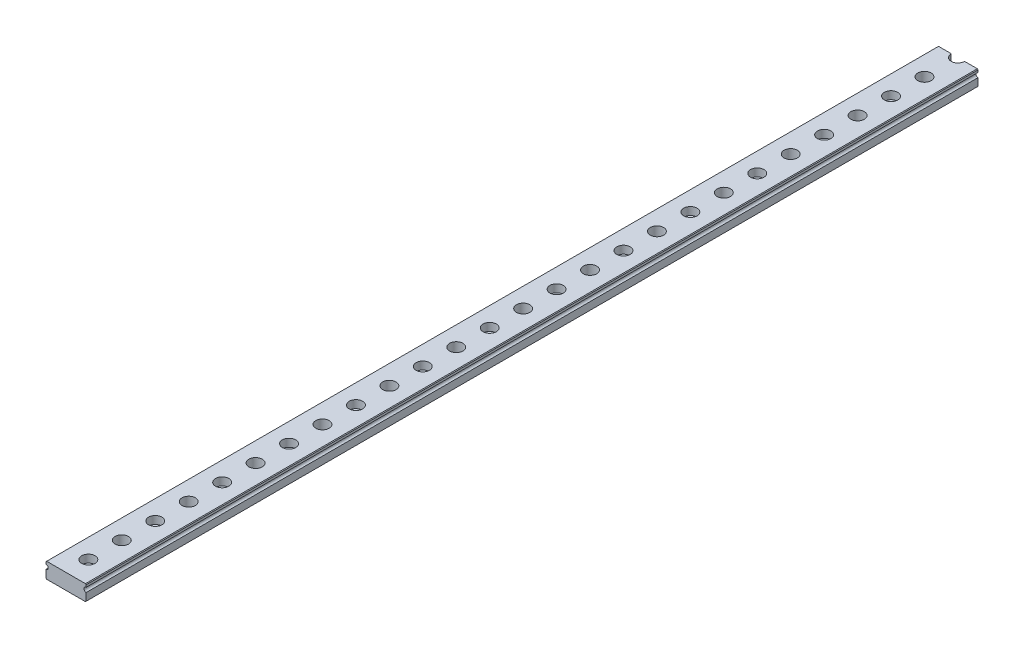
SolidWorks part; units mm, degrees
material "AISI 1020"
ref_plane "Front Plane" through (0, 0, 0) normal (0, 0, 1) x (1, 0, 0)
ref_plane "Top Plane" through (0, 0, 0) normal (0, 1, 0) x (1, 0, 0)
ref_plane "Right Plane" through (0, 0, 0) normal (1, 0, 0) x (0, 0, -1)
ref_plane "Plano1" through (0, 0, 0) normal (0, -1, 0) x (1, 0, 0)
sketch "Esboço1" plane through (0, 0, 0) normal (0, -1, 0) x (1, 0, 0)
  line L0 (-18, -400) -> (0, -400)
  line L1 (0, -400) -> (0, 0)
  line L2 (0, 0) -> (-18, 0)
  line L3 (-18, 0) -> (-18, -400)
  dimension "D1" = 400
  dimension "D2" = 18
extrude "Ressalto-extrusão1" add sketch "Esboço1" against normal blind 7
hole_wizard "Furo de diâmetro Ø2.0 (2)1" positions "Esboço5" profile "Esboço4" hole size "Ø2.0" standard "Ansi Metric" end condition through all
sketch "Esboço5" plane through (0, 0, -400) normal (0, 0, -1) x (-1, 0, 0)
  line L0 (0, 0) -> (18, 0) construction
  line L1 (18, 7) -> (18, 0) construction
  point P0 (0, 4.7)
  point P1 (18, 4.7)
  dimension "D1" = 18
  dimension "D2" = 4.7
sketch "Esboço4" plane through (0, 4.7, -400) normal (1, 0, 0) x (0, 1, 0)
  line L0 (0, 0) -> (0, 400)
  line L1 (0, 400) -> (1, 400)
  line L2 (1, 400) -> (1, 0)
  line L5 (1, 0) -> (0, 0)
  line L11 (0, -6.35) -> (0, 107.95) construction
  dimension "Thru Hole Dia." = 2
  dimension "Thru Hole Depth" = 400
hole_wizard "Furo de diâmetro Ø6.0 (6)1" positions "Esboço3" profile "Esboço2" hole size "Ø6.0" standard "Ansi Metric" end condition through all
sketch "Esboço3" plane through (0, 7, 0) normal (0, 1, 0) x (1, 0, 0)
  line L0 (0, 400) -> (0, 0) construction
  line L1 (0, 0) -> (-18, 0) construction
  point P0 (-9, 25)
  dimension "D3" = 9
  dimension "D4" = 25
sketch "Esboço2" plane through (-9, 7, -25) normal (1, 0, 0) x (0, 0, 1)
  line L0 (0, 0) -> (0, 7)
  line L1 (0, 7) -> (3, 7)
  line L2 (3, 7) -> (3, 0)
  line L5 (3, 0) -> (0, 0)
  line L11 (0, -6.35) -> (0, 107.95) construction
  dimension "Thru Hole Dia." = 6
  dimension "Thru Hole Depth" = 7
hole_wizard "Rebaixo para parafuso de máquina de cabeça sextavada de M31" positions "Esboço9" profile "Esboço8" counterbore size "M3" standard "Ansi Metric" end condition through all
sketch "Esboço9" plane through (0, 7, 0) normal (0, 1, 0) x (1, 0, 0)
  line L0 (0, 400) -> (0, 0) construction
  line L3 (0, 0) -> (-18, 0) construction
  point P2 (-9, 10)
  dimension "D3" = 9
  dimension "D6" = 10
sketch "Esboço8" plane through (-9, 7, -10) normal (1, 0, 0) x (0, 0, 1)
  line L0 (0, 0) -> (0, 7)
  line L1 (0, 7) -> (1.75, 7)
  line L3 (1.75, 7) -> (1.75, 3.5)
  line L4 (1.75, 3.5) -> (3, 3.5)
  line L5 (3, 3.5) -> (3, 0)
  line L7 (3, 0) -> (0, 0)
  line L11 (0, -6.35) -> (0, 107.95) construction
  dimension "Thru Hole Dia." = 3.5
  dimension "Thru Hole Depth" = 7
  dimension "C'Bore Dia." = 6
  dimension "C'Bore Depth" = 3.5
pattern_linear "Padrão linear1" count 13 spacing 30 along (0, 0, -1) of "Furo de diâmetro Ø6.0 (6)1"
pattern_linear "Padrão linear2" count 14 spacing 30 along (0, 0, -1) of "Rebaixo para parafuso de máquina de cabeça sextavada de M31"
chamfer "Chanfro1" distance 0.3 angle 45 4 edges at (-18, 7, -200) (0, 7, -200) (0, 0, -200) (-18, 0, -200)
